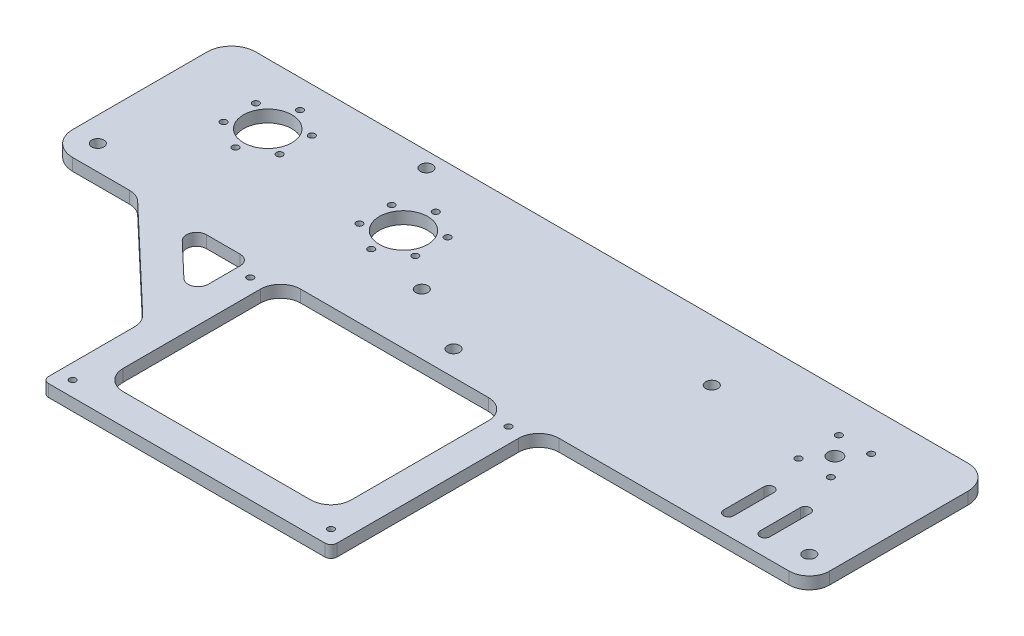
SolidWorks part; units mm, degrees
ref_plane "Plano frontal" through (0, 0, 0) normal (0, 0, 1) x (1, 0, 0)
ref_plane "Plano superior" through (0, 0, 0) normal (0, 1, 0) x (1, 0, 0)
ref_plane "Plano direito" through (0, 0, 0) normal (1, 0, 0) x (0, 0, -1)
sketch "Esboço1" plane through (0, 0, 0) normal (0, 1, 0) x (1, 0, 0)
  line L3 (-85.5279, -153.6487) -> (51.4721, -153.6487)
  line L4 (54.4721, -150.6487) -> (54.4721, -108.1025)
  line L6 (188.5279, -40.6487) -> (188.5279, 28)
  line L7 (176.5279, 40) -> (-176.5279, 40)
  line L8 (-188.5279, 28) -> (-188.5279, -38.6487)
  line L9 (-176.5279, -50.6487) -> (-148.4656, -50.6487)
  line L10 (-141.5771, -53.3996) -> (-91.6394, -100.8535)
  line L11 (-88.5279, -108.1025) -> (-88.5279, -150.6487)
  line L12 (-110.1764, -50.6487) -> (-93.5279, -50.6487)
  line L13 (-88.5279, -55.6487) -> (-88.5279, -71.4691)
  line L14 (-96.9722, -75.0936) -> (-113.6207, -59.2732)
  line L15 (39.4721, -60.6487) -> (39.4721, -128.6487)
  line L16 (29.4721, -138.6487) -> (-63.5279, -138.6487)
  line L17 (-73.5279, -128.6487) -> (-73.5279, -60.6487)
  line L18 (-63.5279, -50.6487) -> (29.4721, -50.6487)
  line L20 (132.5279, 0) -> (148.5279, 0) construction
  line L21 (132.5279, 0) -> (132.5279, 20) construction
  line L22 (132.5279, 20) -> (148.5279, 20) construction
  line L23 (148.5279, 0) -> (148.5279, 20) construction
  line L24 (132.5279, 0) -> (148.5279, 20) construction
  line L25 (132.5279, 20) -> (148.5279, 0) construction
  line L29 (54.4721, -108.1025) -> (54.4721, -60.6487)
  line L30 (64.4721, -50.6487) -> (178.5279, -50.6487)
  line L31 (156.5279, -40.6487) -> (156.5279, -20.6487) construction
  line L32 (154.0279, -40.6487) -> (154.0279, -20.6487)
  line L33 (159.0279, -40.6487) -> (159.0279, -20.6487)
  line L34 (147.5279, -45.2211) -> (147.5279, -21.4375) construction
  line L36 (138.5279, -40.6487) -> (138.5279, -20.6487) construction
  line L37 (141.0279, -40.6487) -> (141.0279, -20.6487)
  line L38 (136.0279, -40.6487) -> (136.0279, -20.6487)
  circle A0 centre (-81.0279, -58.1487) radius 1.6
  circle A1 centre (-81.0279, -146.1487) radius 1.6
  circle A2 centre (46.9721, -58.1487) radius 1.6
  circle A3 centre (46.9721, -146.1487) radius 1.6
  circle A8 centre (176.311, -38.4318) radius 3
  circle A9 centre (0, -38.4318) radius 3
  circle A11 centre (-140.5279, 10) radius 12
  circle A20 centre (-140.5279, 10) radius 16 construction
  circle A21 centre (-140.5279, -6) radius 1.6
  circle A22 centre (-154.3843, 2) radius 1.6
  circle A23 centre (-154.3843, 18) radius 1.6
  circle A24 centre (-84.3674, 32.5) radius 3
  circle A25 centre (-176.311, -38.4318) radius 3
  circle A26 centre (140.5279, 10) radius 3.5
  circle A27 centre (148.5279, 0) radius 1.6
  circle A28 centre (148.5279, 20) radius 1.6
  circle A29 centre (132.5279, 0) radius 1.6
  circle A30 centre (132.5279, 20) radius 1.6
  arc A31 (51.4721, -153.6487) -> (54.4721, -150.6487) centre (51.4721, -150.6487) ccw
  arc A34 (188.5279, 28) -> (176.5279, 40) centre (176.5279, 28) ccw
  arc A35 (-176.5279, 40) -> (-188.5279, 28) centre (-176.5279, 28) ccw
  arc A36 (-188.5279, -38.6487) -> (-176.5279, -50.6487) centre (-176.5279, -38.6487) ccw
  arc A37 (-91.6394, -100.8535) -> (-88.5279, -108.1025) centre (-98.5279, -108.1025) cw
  arc A38 (-88.5279, -150.6487) -> (-85.5279, -153.6487) centre (-85.5279, -150.6487) ccw
  arc A39 (-93.5279, -50.6487) -> (-88.5279, -55.6487) centre (-93.5279, -55.6487) cw
  arc A40 (-88.5279, -71.4691) -> (-96.9722, -75.0936) centre (-93.5279, -71.4691) cw
  arc A41 (-113.6207, -59.2732) -> (-110.1764, -50.6487) centre (-110.1764, -55.6487) cw
  arc A42 (39.4721, -128.6487) -> (29.4721, -138.6487) centre (29.4721, -128.6487) cw
  arc A43 (-63.5279, -138.6487) -> (-73.5279, -128.6487) centre (-63.5279, -128.6487) cw
  arc A44 (-73.5279, -60.6487) -> (-63.5279, -50.6487) centre (-63.5279, -60.6487) cw
  arc A45 (29.4721, -50.6487) -> (39.4721, -60.6487) centre (29.4721, -60.6487) cw
  circle A46 centre (-140.5279, 26) radius 1.6
  circle A47 centre (-126.6715, 18) radius 1.6
  circle A48 centre (-126.6715, 2) radius 1.6
  circle A49 centre (-63.2404, 0) radius 16 construction
  circle A50 centre (-63.2404, -16) radius 1.6
  circle A51 centre (-77.0968, -8) radius 1.6
  circle A52 centre (-77.0968, 8) radius 1.6
  circle A53 centre (-63.2404, 16) radius 1.6
  circle A54 centre (-49.384, 8) radius 1.6
  circle A55 centre (-49.384, -8) radius 1.6
  circle A56 centre (-63.2404, 0) radius 12
  circle A57 centre (-33.5279, -20.6487) radius 3
  circle A58 centre (79.5279, 10) radius 3
  arc A61 (-148.4656, -50.6487) -> (-141.5771, -53.3996) centre (-148.4656, -60.6487) cw
  arc A62 (188.5279, -40.6487) -> (178.5279, -50.6487) centre (178.5279, -40.6487) cw
  arc A63 (54.4721, -60.6487) -> (64.4721, -50.6487) centre (64.4721, -60.6487) cw
  arc A64 (154.0279, -40.6487) -> (159.0279, -40.6487) centre (156.5279, -40.6487) ccw
  arc A65 (159.0279, -20.6487) -> (154.0279, -20.6487) centre (156.5279, -20.6487) ccw
  arc A66 (141.0279, -40.6487) -> (136.0279, -40.6487) centre (138.5279, -40.6487) cw
  arc A67 (136.0279, -20.6487) -> (141.0279, -20.6487) centre (138.5279, -20.6487) cw
  point P14 (156.5279, -30.6487)
  point P43 (-140.5279, 10)
  point P70 (-144.4721, -50.6487)
  point P116 (-63.2404, 0)
  point P123 (0, 40)
  point P124 (138.5279, -30.6487)
  dimension "D2" = 3
  dimension "D7" = 10
  dimension "D8" = 12
  dimension "D10" = 90.6487
  dimension "D11" = 61
  dimension "D12" = 77.2875
  dimension "D13" = 7.5
  dimension "D14" = 104.1605
  dimension "D16" = 12
  dimension "D20" = 10
  dimension "D21" = 3
  dimension "D22" = 48.4318
  dimension "D23" = 32
  dimension "D24" = 3.2
  dimension "D25" = 6
  dimension "D26" = 24
  dimension "D27" = 48
  dimension "D28" = 30
  dimension "D29" = 40
  dimension "D30" = 6
  dimension "D34" = 30
  dimension "D31" = 32
  dimension "D32" = 3.2
  dimension "D33" = 24
  dimension "D35" = 6
  dimension "D36" = 155
  dimension "D37" = 30
  dimension "D44" = 7
  dimension "D48" = 10
  dimension "D54" = 143
  dimension "D6" = 10
  dimension "D58" = 5
  dimension "D62" = 2.5
  dimension "D1" = 137
  dimension "D3" = 42.5462
  dimension "D9" = 377.0558
  dimension "D15" = 66.6487
  dimension "D17" = 32.0558
  dimension "D18" = 100
  dimension "D19" = 42.5462
  dimension "D38" = 48
  dimension "D39" = 15
  dimension "D40" = 12.2169
  dimension "D41" = 12.2169
  dimension "D42" = 16
  dimension "D43" = 20
  dimension "D45" = 15
  dimension "D46" = 15
  dimension "D47" = 15
  dimension "D49" = 7.5
  dimension "D50" = 7.5
  dimension "D51" = 88
  dimension "D52" = 128
  dimension "D53" = 93
  dimension "D55" = 15
  dimension "D56" = 20.6487
  dimension "D57" = 68
  dimension "D59" = 32
  dimension "D60" = 10
  dimension "D61" = 20
  dimension "D63" = 9
extrude "Ressalto-extrusão1" add sketch "Esboço1" against normal blind 6
